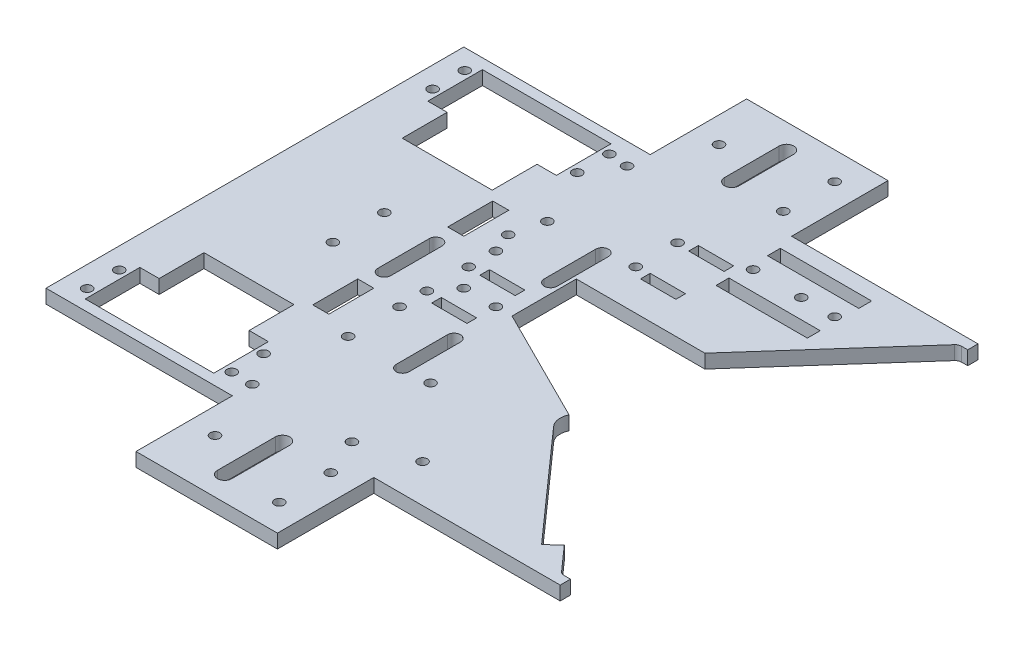
SolidWorks part; units mm, degrees
material "Acrylic (Medium-high impact)"
ref_plane "Front Plane" through (0, 0, 0) normal (0, 0, 1) x (1, 0, 0)
ref_plane "Top Plane" through (0, 0, 0) normal (0, 1, 0) x (1, 0, 0)
ref_plane "Right Plane" through (0, 0, 0) normal (1, 0, 0) x (0, 0, -1)
sketch "Sketch2" plane through (0, 0, 0) normal (0, 1, 0) x (1, 0, 0)
  line L2 (0, 0) -> (0, 65)
  line L3 (0, 65) -> (58, 65)
  line L4 (160, 0) -> (160, 65)
  line L8 (0, 0) -> (160, 0)
  line L9 (102, 65) -> (160, 65)
  line L11 (102, 65) -> (102, 95)
  line L12 (58, 65) -> (58, 95)
  line L13 (58, 95) -> (102, 95)
  dimension "D1" = 65
  dimension "D2" = 160
  dimension "D3" = 44
  dimension "D4" = 30
extrude "Boss-Extrude1" add sketch "Sketch2" along normal blind 4.3
mirror "Mirror1" about plane through (0, 4.3, 0) normal (0, 0, -1) of bodies 101
sketch "Sketch3" plane through (0, 4.3, 0) normal (0, 1, 0) x (1, 0, 0)
  line L0 (160, 61.8) -> (160, -61.8)
  line L1 (120.0126, 20) -> (157.1565, 61.8)
  line L3 (80.0126, 0) -> (80.0126, 20)
  line L4 (80.0126, 20) -> (120.0126, 20)
  line L12 (160, 65) -> (102, 65)
  line L13 (102, 65) -> (102, 95)
  line L15 (102, 95) -> (58, 95)
  line L16 (58, 65) -> (0, 65)
  line L17 (0, 65) -> (0, -65)
  line L18 (0, -65) -> (58, -65)
  line L20 (58, 95) -> (58, 65)
  line L22 (102, -65) -> (160, -65)
  line L23 (160, -65) -> (160, 65)
  line L36 (58, -65) -> (58, -95)
  line L38 (58, -95) -> (102, -95)
  line L39 (58, -95) -> (102, -95)
  line L40 (102, -95) -> (102, -65)
  line L42 (160, -61.8) -> (157.1556, -61.8)
  line L45 (160, 61.8) -> (157.1565, 61.8)
  line L48 (80.0126, 0) -> (120, -20)
  line L49 (120, -20) -> (157.1556, -61.8)
  line M24 (160, -65) -> (160, 65)
  dimension "D2" = 130
  dimension "D3" = 20
  dimension "D4" = 40
  dimension "D1" = 0
extrude "Cut-Extrude1" cut sketch "Sketch3" against normal blind 4.5 contours L48 L49 L1 L4 L3 M24 region at (132.7054, 4.3, -1.1594)
fillet "Fillet1" radius 2 2 edges at (157.1565, 2.15, -61.8) (157.1556, 2.15, 61.8)
ref_axis "Axis1" through (80, 4.3, 95) along (0, 0, -1)
sketch "Sketch4" plane through (0, 4.3, 0) normal (0, 1, 0) x (1, 0, 0)
  line L0 (80, -95) -> (80, 95)
  line L1 (102, -95) -> (58, -95) construction
  line L2 (102, 95) -> (58, 95) construction
ref_plane "Plane2" through (0, 4.3, 0) normal (0, 1, 0) x (1, 0, 0)
sketch "Sketch6" plane through (0, 4.3, 0) normal (0, 1, 0) x (1, 0, 0)
  line L3 (9, -61.8) -> (49, -61.8)
  line L6 (29, -45.8) -> (29, -44.8)
  line L7 (9, -44.8) -> (15, -44.8)
  line L11 (43, -44.8) -> (43, -30.8418)
  line L12 (15, -44.8) -> (15, -30.8418)
  line L13 (15, -30.8418) -> (43, -30.8418)
  line L15 (0, 0) -> (80.0126, 0)
  line L16 (80.0126, 0) -> (120, -20) construction
  line L18 (9, 44.8) -> (15, 44.8)
  line L20 (15, 30.8418) -> (43, 30.8418)
  line L21 (15, 44.8) -> (15, 30.8418)
  line L22 (43, 44.8) -> (43, 30.8418)
  line L25 (15, -45.8) -> (15, -30.8418) construction
  line L27 (9, 61.8) -> (49, 61.8)
  line L30 (4, -61.8) -> (3, -61.8)
  line L31 (0, -61.8) -> (160, -61.8) construction
  line L32 (3, -61.8) -> (4, -61.8)
  line L33 (3, -44.8) -> (3, -62.8) construction
  line L34 (3, -62.8) -> (55, -62.8) construction
  line L35 (55, -44.8) -> (55, -62.8) construction
  line L36 (4, -61.8) -> (54, -61.8) construction
  line L37 (0, 61.8) -> (160, 61.8) construction
  line L38 (54, 61.8) -> (55, 61.8)
  line L39 (54, 61.8) -> (55, 61.8)
  line L40 (43, 44.8) -> (49, 44.8)
  line L41 (4, -45.8) -> (4, -61.8) construction
  line L42 (4, -45.8) -> (54, -45.8) construction
  line L43 (43, -44.8) -> (49, -44.8)
  line L44 (3, -44.8) -> (55, -44.8) construction
  line L45 (29, -45.8) -> (29, -30.8418) construction
  line L46 (43, -45.8) -> (43, -30.8418) construction
  line L47 (54, -45.8) -> (54, -61.8) construction
  line L48 (9, -61.8) -> (49, -61.8)
  line L52 (9, 61.8) -> (9, 44.8)
  line L53 (55, 61.8) -> (54, 61.8)
  line L56 (49, 61.8) -> (49, 44.8)
  line L59 (3, -61.8) -> (4, -61.8)
  line L60 (9, -44.8) -> (9, -61.8)
  line L64 (49, -44.8) -> (49, -61.8)
  dimension "D4" = 1
  dimension "D5" = 14
  dimension "D6" = 14
extrude "Cut-Extrude2" cut sketch "Sketch6" against normal blind 10
sketch "Sketch8" plane through (0, 4.3, 0) normal (0, 1, 0) x (1, 0, 0)
  circle A0 centre (6.5, 58.8) radius 1.5
  circle A1 centre (6.5, 48.8) radius 1.5
  circle A2 centre (51.5, 48.8) radius 1.5
  circle A3 centre (51.5, 58.8) radius 1.5
  circle A4 centre (6.5, -48.7) radius 1.5
  circle A5 centre (6.5, -58.7) radius 1.5
  circle A6 centre (51.5, -58.7) radius 1.5
  circle A7 centre (51.5, -48.8) radius 1.5
  dimension "D7" = 3
extrude "Cut-Extrude3" cut sketch "Sketch8" against normal blind 10
sketch "Sketch9" plane through (0, 0, 0) normal (0, -1, 0) x (1, 0, 0)
  line L0 (75.75, 69.4) -> (75.75, 87.4)
  line L1 (75.75, -87.4) -> (75.75, -70.4)
  line L2 (80.25, -87.4) -> (80.25, -70.4)
  line L4 (80.25, 69.4) -> (80.25, 87.4)
  circle A0 centre (94, 70.4) radius 1.5
  circle A1 centre (66, 78.4) radius 1.5
  circle A2 centre (66, -78.4) radius 1.5
  circle A3 centre (94, -86.4) radius 1.5
  circle A4 centre (94, 86.4) radius 1.5
  circle A5 centre (94, -70.4) radius 1.5
  arc A6 (75.75, -87.4) -> (80.25, -87.4) centre (78, -87.4) ccw
  arc A7 (80.25, -70.4) -> (75.75, -70.4) centre (78, -70.4) ccw
  arc A10 (75.75, 69.4) -> (80.25, 69.4) centre (78, 69.4) ccw
  arc A12 (80.25, 87.4) -> (75.75, 87.4) centre (78, 87.4) ccw
  dimension "D1" = 3
extrude "Cut-Extrude4" cut sketch "Sketch9" against normal blind 10
sketch "Sketch7" plane through (0, 4.3, 0) normal (0, 1, 0) x (1, 0, 0)
  line L0 (0, 0) -> (80.0126, 0)
  line L1 (0, 65) -> (0, -65) construction
  line L2 (80.0126, 0) -> (80.0126, 20) construction
  line L3 (80, -95) -> (80, 95) construction
  line L4 (64, -9) -> (75, -9)
  line L5 (64, -6) -> (75, -6)
  line L6 (64, -9) -> (64, -6)
  line L7 (75, -9) -> (75, -6)
  line L8 (64, -7.5) -> (75, -7.5)
  line L9 (64, 7.5) -> (75, 7.5)
  line L10 (75, 9) -> (75, 6)
  line L11 (64, 9) -> (64, 6)
  line L12 (64, 6) -> (75, 6)
  line L13 (64, 9) -> (75, 9)
  line L14 (89.9874, 30) -> (100.9874, 30)
  line L15 (89.9874, 33) -> (100.9874, 33)
  line L16 (89.9874, 30) -> (89.9874, 33)
  line L17 (100.9874, 30) -> (100.9874, 33)
  line L20 (100.9874, 48) -> (100.9874, 45)
  line L21 (89.9874, 48) -> (89.9874, 45)
  line L22 (89.9874, 45) -> (100.9874, 45)
  line L23 (89.9874, 48) -> (100.9874, 48)
  line L24 (80.0126, 20) -> (120.0126, 20) construction
  circle A0 centre (60.0126, -6.5) radius 1.5
  circle A1 centre (60.0126, 6.5) radius 1.5
  circle A2 centre (86, 32.5) radius 1.5
  circle A3 centre (86, 45.5) radius 1.5
  dimension "D1" = 3
  dimension "D8" = 3
  dimension "D2" = 6.5
  dimension "D3" = 20
  dimension "D6" = 11
  dimension "D4" = 5
  dimension "D5" = 3
  dimension "D7" = 7.5
  dimension "D9" = 11
  dimension "D10" = 3
  dimension "D11" = 12
  dimension "D12" = 13
  dimension "D13" = 10
  dimension "D14" = 3.9874
  dimension "D15" = 0.5
  dimension "D16" = 0.5
  dimension "D17" = 3.9874
  dimension "D18" = 6
  dimension "D19" = 11
sketch "Sketch10" plane through (0, 4.3, 0) normal (0, 1, 0) x (1, 0, 0)
  line L0 (120, -20) -> (156.5589, -61.1287) construction
  line L1 (123.3218, -23.737) -> (149.8964, -53.6334)
  line L2 (116.263, -23.3218) -> (146.1593, -56.9552)
  line L3 (149.8964, -53.6334) -> (146.1593, -56.9552)
  line L4 (120, -20) -> (156.5589, -61.1287) construction
  line L5 (116.263, -23.3218) -> (152.8218, -64.4505) construction
  arc A0 (123.3218, -23.737) -> (116.263, -23.3218) centre (120, -20) ccw
  dimension "D1" = 5
  dimension "D2" = 45
extrude "Cut-Extrude5" cut sketch "Sketch10" against normal blind 10
sketch "Sketch11" plane through (0, 0, 0) normal (0, -1, 0) x (1, 0, 0)
  line L0 (0, 0) -> (80.0126, 0) construction
  line L1 (80, 95) -> (80, -95) construction
  line L2 (80.0126, 0) -> (0, 0)
  line L4 (75, 31.0313) -> (75, 15.0313)
  line L6 (79, 31.0313) -> (79, 15.0313)
  line L7 (79, -31.0313) -> (79, -15.0313)
  line L8 (75, -31.0313) -> (75, -15.0313)
  circle A0 centre (60, 31) radius 1.5
  circle A1 centre (60, 15) radius 1.5
  arc A2 (75, 31.0313) -> (79, 31.0313) centre (77, 31.0313) cw
  arc A3 (75, 15.0313) -> (79, 15.0313) centre (77, 15.0313) ccw
  arc A4 (75, -15.0313) -> (79, -15.0313) centre (77, -15.0313) cw
  arc A5 (75, -31.0313) -> (79, -31.0313) centre (77, -31.0313) ccw
  circle A6 centre (60, -15) radius 1.5
  circle A7 centre (60, -31) radius 1.5
  dimension "D1" = 3
  dimension "D2" = 16
  dimension "D3" = 15
  dimension "D4" = 20
  dimension "D5" = 15
  dimension "D6" = 4
extrude "Cut-Extrude6" cut sketch "Sketch11" against normal blind 10 contours L4 A3 L6 A2 | L8 A5 L7 A4 | A7 | A0 | A1 | A6 region at (77, 0, 23.0313) region at (77, 0, -23.0313) region at (60, 0, -31)
sketch "Sketch12" plane through (0, 0, 0) normal (0, -1, 0) x (-1, 0, 0)
  line L0 (0, 0) -> (-80.0126, 0) construction
  line L3 (-50.2627, -8) -> (-50.2627, 8)
  line L4 (-50.2627, 0) -> (-46.2627, 0)
  line L5 (-46.2627, -8) -> (-46.2627, 8)
  line L6 (0, 0) -> (-46.2627, 0)
  line L7 (0, 65) -> (0, -65) construction
  line L8 (-160, -61.8) -> (0, -61.8) construction
  line L9 (-80.0126, 0) -> (-50.2627, 0)
  line L10 (-80.0126, 0) -> (-115.5281, -17.7634) construction
  line L11 (-80.0126, 0) -> (-80.0126, 20) construction
  line L12 (-58, -65) -> (0, -65) construction
  line L13 (-58, 65) -> (0, 65) construction
  circle A0 centre (-32.2627, -8) radius 1.5
  circle A1 centre (-32.2627, 8) radius 1.5
  arc A2 (-46.2627, 8) -> (-50.2627, 8) centre (-48.2627, 8) ccw
  arc A3 (-50.2627, -8) -> (-46.2627, -8) centre (-48.2627, -8) ccw
  circle A5 centre (-32.2627, -8) radius 1.5 construction
  circle A6 centre (-32.2627, 8) radius 1.5 construction
  dimension "D1" = 3
  dimension "D8" = 8
  dimension "D9" = 8
  dimension "D2" = 8
  dimension "D3" = 14
  dimension "D4" = 4
  dimension "D5" = 61.8
  dimension "D6" = 65
  dimension "D7" = 65
extrude "Cut-Extrude7" cut sketch "Sketch12" against normal blind 10 contours A3 L5 L4 L3 | L4 L5 A2 L3 | A0 | A1 region at (48.2627, 0, 4.7958) region at (48.2627, 0, -4.7958) region at (32.2627, 0, 8) region at (32.2627, 0, -8)
extrude "Cut-Extrude8" cut sketch "Sketch7" against normal blind 9 contours A0 | L4 L7 L5 L6 | L12 L10 L13 L11 | A1 | L23 L20 L22 L21 | L15 L17 L14 L16 | A3 | A2
sketch "Sketch13" plane through (0, 4.3, 0) normal (0, 1, 0) x (1, 0, 0)
  line L0 (80.0126, 0) -> (59.0194, 0)
  line L1 (80, -95) -> (80, 95) construction
  circle A0 centre (65, 0) radius 1.5
  circle A1 centre (75, 0) radius 1.5
  dimension "D2" = 3
  dimension "D3" = 5
  dimension "D1" = 10
extrude "Cut-Extrude9" cut sketch "Sketch13" against normal blind 10 contours L0 A0 | L0 A0 | L0 A1 | L0 A1 region at (75, 4.3, 0.6366) region at (75, 4.3, -0.6366) region at (65, 4.3, 0.6366) region at (65, 4.3, -0.6366)
sketch "Sketch14" plane through (0, 4.3, 0) normal (0, 1, 0) x (1, 0, 0)
  circle A0 centre (57.5, 58.3) radius 1.5
  circle A2 centre (57.5, 21.3) radius 1.5
  circle A3 centre (85.37, -30.7129) radius 1.5
  circle A4 centre (105.301, -53.1351) radius 1.5
  dimension "D1" = 3
  dimension "D2" = 3
extrude "Cut-Extrude10" cut sketch "Sketch14" against normal blind 10
sketch "Sketch15" plane through (0, 4.3, 0) normal (0, 1, 0) x (1, 0, 0)
  line L1 (46, 28) -> (51, 28)
  line L2 (46, 28) -> (46, 14)
  line L3 (46, 14) -> (51, 14)
  line L4 (51, 28) -> (51, 14)
  line L6 (0, 65) -> (0, -65) construction
  line L7 (80.0126, 0) -> (53.7017, 0)
  line L8 (46, -14) -> (51, -14)
  line L9 (51, -28) -> (51, -14)
  line L10 (46, -28) -> (51, -28)
  line L11 (46, -28) -> (46, -14)
  arc A0 (50.2627, 8) -> (46.2627, 8) centre (48.2627, 8) ccw construction
  arc A1 (46.2627, -8) -> (50.2627, -8) centre (48.2627, -8) ccw construction
  dimension "D1" = 46
  dimension "D2" = 5
  dimension "D3" = 14
  dimension "D4" = 14
  dimension "D5" = 14
  dimension "D6" = 6
  dimension "D7" = 6
extrude "Cut-Extrude11" cut sketch "Sketch15" against normal blind 10 contours L4 L1 L2 L3 | L11 L10 L9 L8 region at (48.5, 4.3, -21) region at (48.5, 4.3, 21)
sketch "Sketch16" plane through (0, 4.3, 0) normal (0, 1, 0) x (1, 0, 0)
  circle A0 centre (89, -58.8) radius 1.5
  circle A1 centre (58, -58.8) radius 1.5
  dimension "D1" = 3
extrude "Cut-Extrude12" cut sketch "Sketch16" against normal blind 10
ref_plane "Plane3" through (44.2426, 0, 0) normal (1, 0, 0) x (0, 0, -1)
sketch "Sketch17" plane through (44.2426, 0, 0) normal (1, 0, 0) x (0, 0, -1)
  line L4 (0, 0) -> (20, 0)
  line L5 (20, 0) -> (20, 4.3)
  line L6 (20, 4.3) -> (0, 4.3)
  line L7 (0, 4.3) -> (0, 0)
  line L8 (0, 0) -> (20, 0)
  line L9 (20, 0) -> (20, 4.3)
  line L10 (20, 4.3) -> (0, 4.3)
  line L11 (0, 4.3) -> (0, 0)
  circle A0 centre (-2.83, 16.28) radius 0.5
  point P6 (0, 2.15)
  dimension "D4" = 1
  dimension "D2" = 2.83
  dimension "D3" = 14.13
  dimension "D1" = 0
sketch "Sketch18" plane through (0, 4.3, 0) normal (0, 1, 0) x (1, 0, 0)
  line L0 (121.5, 50) -> (128.9, 50)
  line L1 (103.5, 60) -> (131.9, 60)
  line L2 (102, 65) -> (102, 95) construction
  line L3 (160, 65) -> (102, 65) construction
  line L4 (103.5, 60) -> (103.5, 56)
  line L5 (106.5, 50) -> (118.5, 50)
  line L6 (131.9, 60) -> (131.9, 56)
  line L7 (103.5, 60) -> (131.9, 60)
  line L8 (103.5, 60) -> (103.5, 56)
  line L9 (103.5, 56) -> (131.9, 56)
  line L10 (131.9, 60) -> (131.9, 56)
  line L11 (103.5, 44) -> (131.9, 44)
  line L12 (131.9, 40) -> (131.9, 44)
  line L13 (103.5, 40) -> (131.9, 40)
  line L14 (103.5, 40) -> (103.5, 44)
  circle A0 centre (105, 50) radius 1.5
  circle A1 centre (120, 50) radius 1.5
  circle A3 centre (130.4, 50) radius 1.5
  dimension "D1" = 3
  dimension "D6" = 3
  dimension "D2" = 15
  dimension "D4" = 3
  dimension "D5" = 15
  dimension "D7" = 25.4
  dimension "D8" = 4
  dimension "D9" = 6
extrude "Cut-Extrude13" cut sketch "Sketch18" against normal blind 10 contours L4 L9 L6 L1 | A0 | A1 | A3 | L14 L13 L12 L11 region at (130.4, 4.3, -50) region at (120, 4.3, -50) region at (105, 4.3, -50) region at (117.7, 4.3, -58) region at (117.7, 4.3, -42)
